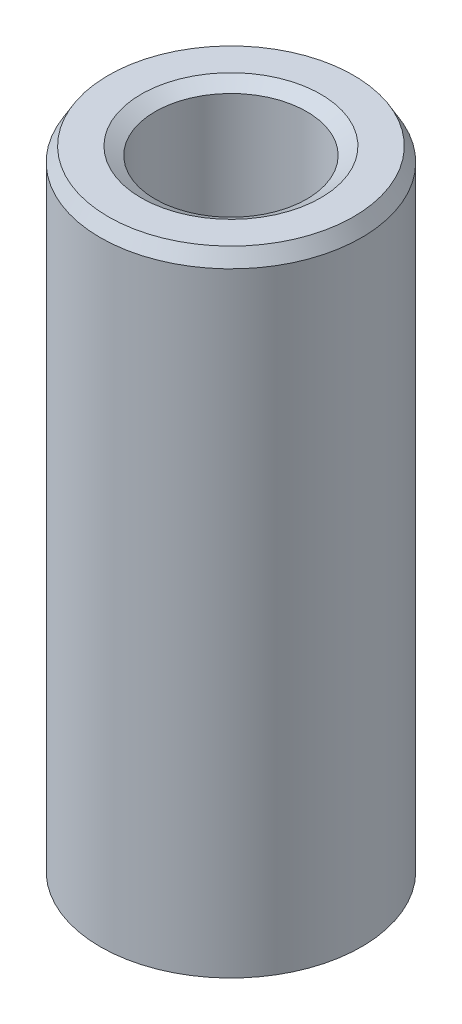
SolidWorks part; units mm, degrees
ref_plane "Front Plane" through (0, 0, 0) normal (0, 0, 1) x (1, 0, 0)
ref_plane "Top Plane" through (0, 0, 0) normal (0, 1, 0) x (1, 0, 0)
ref_plane "Right Plane" through (0, 0, 0) normal (1, 0, 0) x (0, 0, -1)
sketch "Sketch1" plane through (0, 0, 0) normal (0, 1, 0) x (1, 0, 0)
  circle A0 centre (0, 0) radius 32.5
  dimension "SLEEVE_OD" = 65
extrude "Boss-Extrude1" add sketch "Sketch1" along normal blind 158.2478
sketch "Sketch2" plane through (0, 0, 0) normal (0, 1, 0) x (1, 0, 0)
  circle A0 centre (0, 0) radius 18.8619
  dimension "BORE_D" = 37.7238
extrude "Cut-Extrude1" cut sketch "Sketch2" along normal through all
chamfer "Chamfer1" distance 3.4793 angle 30 4 edges at (0, 158.2478, 18.8619) (0, 0, 18.8619) (0, 0, 32.5) (0, 158.2478, 32.5) first distance on face at (0, 158.2478, 18.8619) first distance on face at (0, 0, 18.8619) first distance on face at (0, 158.2478, 32.5)
